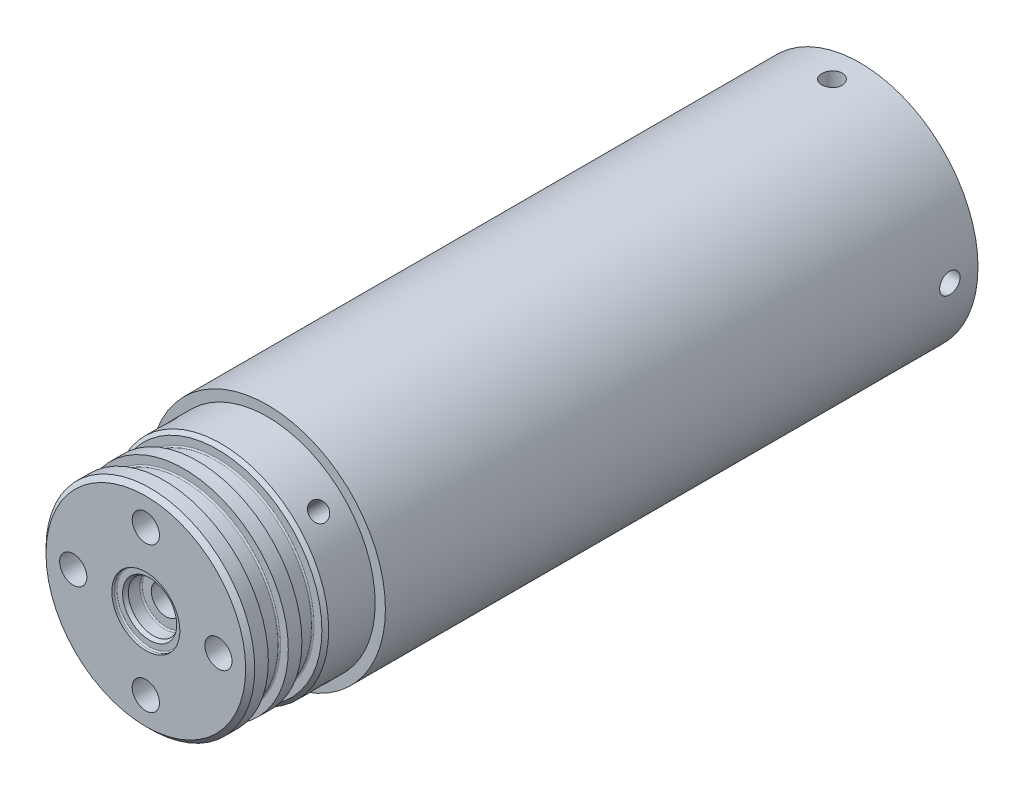
SolidWorks part; units mm, degrees
material "6061-T6 (SS)"
ref_plane "Front Plane" through (0, 0, 0) normal (0, 0, 1) x (1, 0, 0)
ref_plane "Top Plane" through (0, 0, 0) normal (0, 1, 0) x (1, 0, 0)
ref_plane "Right Plane" through (0, 0, 0) normal (1, 0, 0) x (0, 0, -1)
sketch "Sketch8" plane through (0, 0, 0) normal (1, 0, 0) x (0, 0, -1)
  line L0 (-90, 0) -> (90, 0) construction
  line L1 (-90, 20) -> (-31, 20)
  line L2 (-90, 26) -> (90, 26) construction
  line L3 (-90, 20) -> (-90, 22)
  line L7 (0, 26) -> (0, 21)
  line L18 (-63.2, 26) -> (0, 26)
  line L19 (0, 26) -> (0, 21) construction
  line L20 (-63.2, 23.75) -> (-63.2, 26)
  line L22 (-30, 21) -> (-31, 20)
  line L25 (0, 21) -> (-30, 21)
  line L27 (-89, 23) -> (-86, 23)
  line L28 (-86, 23) -> (-86, 21)
  line L29 (-86, 21) -> (-81.6, 21)
  line L30 (-81.6, 21) -> (-81.6, 23)
  line L31 (-81.6, 23) -> (-78.6, 23)
  line L32 (-78.6, 23) -> (-78.6, 21)
  line L33 (-90, 22) -> (-89, 23)
  line L34 (-78.6, 21) -> (-74.2, 21)
  line L35 (-74.2, 21) -> (-74.2, 23)
  line L37 (-73.45, 23.75) -> (-63.2, 23.75)
  line L38 (-74.2, 23) -> (-73.45, 23.75)
  point P4 (0, 0)
  dimension "D20" = 26
  dimension "D1" = 180
  dimension "D2" = 20
  dimension "D3" = 6
  dimension "D4" = 45
  dimension "D5" = 4.4
  dimension "D6" = 4
  dimension "D7" = 1
  dimension "D8" = 0.75
  dimension "D9" = 11
  dimension "D10" = 1
  dimension "D11" = 45
  dimension "D12" = 2.75
  dimension "D21" = 45
  dimension "D22" = 31
  dimension "D23" = 21
  dimension "D24" = 23
  dimension "D26" = 3
  dimension "D27" = 4.4
revolve "Revolve1" add sketch "Sketch8" angle 360 about L0 region at (0, 22.9438, 40.0211)
sketch "Sketch18" plane through (0, 0, 90) normal (0, 0, 1) x (1, 0, 0)
  circle A0 centre (0, 0) radius 20 construction
  circle A1 centre (0, 0) radius 20
  circle A3 centre (0, 0) radius 16 construction
  circle A4 centre (0, 16) radius 1.5
  circle A5 centre (16, 0) radius 1.5
  circle A6 centre (0, -16) radius 1.5
  circle A7 centre (-16, 0) radius 1.5
  point P16 (0, 0)
  dimension "D2" = 32
  dimension "D3" = 3
  dimension "D5" = 16
  dimension "D6" = 16
  dimension "D4" = 4
extrude "Boss-Extrude2" add sketch "Sketch18" against normal blind 25
sketch "Sketch35" plane through (0, 0, 65) normal (0, 0, -1) x (-1, 0, 0)
  circle A0 centre (0, 0) radius 6.4
  dimension "D1" = 12.8
extrude "Cut-Extrude11" cut sketch "Sketch35" against normal blind 15.6
sketch "Sketch25" plane through (0, 0, 90) normal (0, 0, 1) x (1, 0, 0)
  circle A0 centre (0, 16) radius 3
  circle A1 centre (16, 0) radius 3
  circle A2 centre (0, -16) radius 3
  circle A3 centre (-16, 0) radius 3
  point P12 (0, 0)
  dimension "D1" = 6
  dimension "D3" = 16
  dimension "D4" = 16
  dimension "D2" = 4
extrude "Cut-Extrude3" cut sketch "Sketch25" against normal blind 16.5
sketch "Sketch23" plane through (0, 0, 65) normal (0, 0, -1) x (-1, 0, 0)
  circle A0 centre (0, 0) radius 11
  dimension "D1" = 22
extrude "Cut-Extrude2" cut sketch "Sketch23" against normal blind 1.5
sketch "Sketch24" plane through (0, 0, 90) normal (0, 0, 1) x (1, 0, 0)
  circle A2 centre (0, 0) radius 3.25
  circle A5 centre (0, 0) radius 22 construction
  dimension "D1" = 6.5
extrude "Cut-Extrude12" cut sketch "Sketch24" against normal blind 25
sketch "Sketch26" plane through (0, 0, 0) normal (0, 0, -1) x (-1, 0, 0)
  circle A0 centre (0, 0) radius 26 construction
  circle A1 centre (0, 0) radius 26
  circle A2 centre (0, 0) radius 21 construction
  circle A3 centre (0, 0) radius 21
extrude "Boss-Extrude4" add sketch "Sketch26" along normal blind 67.6
sketch "Sketch27" plane through (0, 0, -67.6) normal (0, 0, -1) x (-1, 0, 0)
  circle A0 centre (0, 0) radius 21 construction
  circle A1 centre (0, 0) radius 21
  circle A3 centre (0, 0) radius 22.25
  dimension "D1" = 44.5
extrude "Cut-Extrude4" cut sketch "Sketch27" against normal blind 26.8
sketch "Sketch31" plane through (0, 0, 0) normal (0, 1, 0) x (1, 0, 0)
  line L0 (0, 67.6) -> (0, -89.2) construction
  line L1 (26, 67.6) -> (-26, 67.6) construction
ref_plane "Plane3" through (0, 0, 0) normal (-0.7071, 0.7071, 0) x (0, 0, 1)
ref_plane "Plane4" through (-16.7938, 16.7938, 0) normal (-0.7071, 0.7071, 0) x (0, 0, 1)
sketch "Sketch32" plane through (-16.7938, 16.7938, 0) normal (-0.7071, 0.7071, 0) x (0, 0, 1)
  line L0 (-67.6, 0) -> (89.2, 0) construction
  line L3 (74.2, -23) -> (74.2, 23) construction
  circle A0 centre (68.7, 0) radius 2
  dimension "D1" = 4
  dimension "D2" = 5.5
extrude "Cut-Extrude8" cut sketch "Sketch32" against normal blind 6
pattern_circular "CirPattern2" count 3 over 180 about axis through (0, 0, -67.6) along (0, 0, -1) of "Cut-Extrude8"
ref_plane "Plane6" through (0, 26, 0) normal (0, 1, 0) x (1, 0, 0)
sketch "Sketch38" plane through (0, 26, 0) normal (0, 1, 0) x (1, 0, 0)
  line L0 (0, 67.6) -> (0, 0) construction
  line L1 (26, 67.6) -> (-26, 67.6) construction
  line L2 (22.25, 67.6) -> (-22.25, 67.6) construction
  circle A0 centre (0, 61.2) radius 2.25
  dimension "D1" = 4.5
  dimension "D2" = 6.4
extrude "Cut-Extrude14" cut sketch "Sketch38" against normal blind 10
pattern_circular "CirPattern3" count 4 over 360 about axis through (0, 0, -67.6) along (0, 0, -1) of "Cut-Extrude14"
sketch "Sketch39" plane through (0, 0, 90) normal (0, 0, 1) x (1, 0, 0)
  circle A0 centre (0, 0) radius 5.5
  dimension "D1" = 11
extrude "Cut-Extrude15" cut sketch "Sketch39" against normal blind 4.45
sketch "Sketch40" plane through (0, 0, 90) normal (0, 0, 1) x (1, 0, 0)
  circle A0 centre (0, 0) radius 7.5
  dimension "D1" = 15
extrude "Cut-Extrude16" cut sketch "Sketch40" against normal blind 0.85
sketch "Sketch45" plane through (0, 0, -67.6) normal (0, 0, -1) x (-1, 0, 0)
  circle A0 centre (0, 0) radius 22.45
  dimension "D1" = 44.9
extrude "Cut-Extrude20" cut sketch "Sketch45" against normal up to surface (26.8 mm away) up to face at (-21, 0, -40.8)
sketch "Sketch46" plane through (0, 0, -67.6) normal (0, 0, -1) x (-1, 0, 0)
  circle A1 centre (0, 0) radius 26 construction
  circle A2 centre (0, 0) radius 26
extrude "Cut-Extrude21" cut sketch "Sketch46" against normal blind 0.2
chamfer "Chamfer4" distance 1.5 angle 45 1 edges at (-21, 0, -40.8)
fillet "Fillet1" radius 0.3 4 edges at (21, 0, 81.6) (21, 0, 86) (21, 0, 78.6) (21, 0, 74.2)
sketch "Sketch47" plane through (0, 0, 0) normal (1, 0, 0) x (0, 0, -1)
  line L0 (-90, 0) -> (67.4, 0) construction
  line L1 (-90, 7.5) -> (-90, -7.5) construction
  line L2 (67.4, -22.45) -> (67.4, 22.45) construction
  line L3 (-89.15, 5.9619) -> (-89.15, 5.5)
  line L4 (-89.15, 7.5) -> (-89.15, -7.5) construction
  line L5 (-89.15, 5.5) -> (-89.15, -5.5) construction
  line L6 (-89.15, 5.5) -> (-88.35, 5.5)
  line L7 (-88.35, 5.5) -> (-89.15, 5.9619)
  dimension "D1" = 0.8
  dimension "D2" = 30
  dimension "D3" = 5.5
revolve "Cut-Revolve1" cut sketch "Sketch47" angle 360 about L0
fillet "Fillet2" radius 0.3 2 edges at (5.5, 0, 85.55) (7.5, 0, 89.15)
